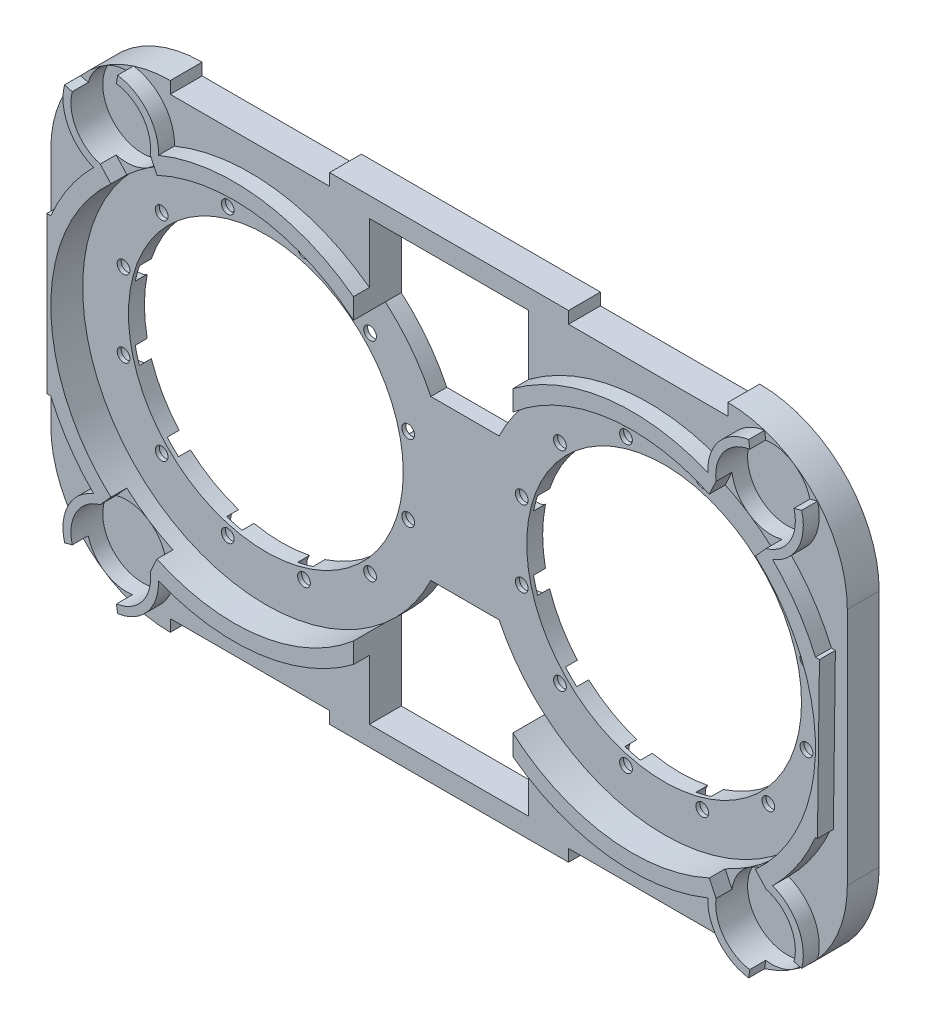
SolidWorks part; units mm, degrees
ref_plane "前视基准面" through (0, 0, 0) normal (0, 0, 1) x (1, 0, 0)
ref_plane "上视基准面" through (0, 0, 0) normal (0, 1, 0) x (1, 0, 0)
ref_plane "右视基准面" through (0, 0, 0) normal (1, 0, 0) x (0, 0, -1)
sketch "草图1" plane through (0, 0, 0) normal (0, 0, 1) x (1, 0, 0)
  line L0 (100, 30) -> (100, -30)
  line L1 (-20, -55) -> (20, -55)
  line L2 (-70, -60) -> (70, -60)
  line L3 (0, -20) -> (-8.5754, -20)
  line L4 (-100, 30) -> (-100, -30)
  line L10 (-70, 60) -> (70, 60)
  line L12 (8.5754, -20) -> (0, -20)
  line L13 (20, -55) -> (20, -34.8712)
  line L14 (-20, -55) -> (-20, -34.8712)
  line L16 (-20, 55) -> (20, 55)
  line L17 (-20, 55) -> (-20, 34.8712)
  line L18 (20, 55) -> (20, 34.8712)
  line L19 (8.5754, 20) -> (0, 20)
  line L20 (0, 20) -> (-8.5754, 20)
  circle A0 centre (-50, 0) radius 34.5
  circle A1 centre (50, 0) radius 34.5
  arc A2 (-100, 30) -> (-70, 60) centre (-70, 30) cw
  arc A3 (-100, -30) -> (-70, -60) centre (-70, -30) ccw
  arc A4 (100, -30) -> (70, -60) centre (70, -30) cw
  arc A5 (100, 30) -> (70, 60) centre (70, 30) ccw
  arc A8 (-8.5754, -20) -> (-20, -34.8712) centre (-50, 0) cw
  arc A9 (8.5754, -20) -> (20, -34.8712) centre (50, 0) ccw
  arc A10 (8.5754, 20) -> (20, 34.8712) centre (50, 0) cw
  arc A11 (-8.5754, 20) -> (-20, 34.8712) centre (-50, 0) ccw
  point P3 (0, -60)
  point P17 (-100, 0)
extrude "面板" add sketch "草图1" against normal blind 4 contours L0 A5 L10 A2 L4 A3 L2 A4 A1 A0 L12 A9 L13 L1 L14 A8 L3 L20 A11 L17 L16 L18 A10 L19 region at (0, 0, 0)
sketch "草图2" plane through (0, 0, 0) normal (0, 0, 1) x (1, 0, 0)
  line L0 (-100, 30) -> (-100, -30)
  line L3 (20, 55) -> (20, 34.8712)
  line L6 (-70, 60) -> (70, 60)
  line L7 (20, 55) -> (-20, 55)
  line L9 (-20, 55) -> (-20, 34.8712)
  line L12 (-70, -60) -> (70, -60)
  line L17 (100, 30) -> (100, -30)
  line L18 (8.5754, 20) -> (-8.5754, 20)
  line L25 (-20, -55) -> (-20, -34.8712)
  line L26 (8.5754, -20) -> (-8.5754, -20)
  line L27 (20, -55) -> (-20, -55)
  line L28 (20, -55) -> (20, -34.8712)
  arc A1 (-100, 30) -> (-70, 60) centre (-70, 30) cw
  arc A2 (-70, 60) -> (-100, 30) centre (-70, 30) ccw construction
  arc A4 (-100, -30) -> (-70, -60) centre (-70, -30) ccw
  arc A5 (100, -30) -> (70, -60) centre (70, -30) cw
  arc A7 (100, 30) -> (70, 60) centre (70, 30) ccw
  circle A20 centre (50, 0) radius 33
  circle A21 centre (-50, 0) radius 33
  arc A22 (8.5754, 20) -> (20, 34.8712) centre (50, 0) cw
  arc A23 (20, 34.8712) -> (8.5754, 20) centre (50, 0) ccw construction
  arc A24 (-8.5754, 20) -> (-20, 34.8712) centre (-50, 0) ccw
  arc A25 (-8.5754, 20) -> (-20, 34.8712) centre (-50, 0) ccw construction
  arc A26 (-8.5754, -20) -> (-20, -34.8712) centre (-50, 0) cw
  arc A27 (8.5754, -20) -> (20, -34.8712) centre (50, 0) ccw
  circle A28 centre (-50, 0) radius 46
  circle A29 centre (50, 0) radius 46
  circle A32 centre (80.95, 46.6721) radius 10
  circle A35 centre (-80.95, 46.6721) radius 10
  circle A36 centre (80.95, -46.6721) radius 10
  circle A37 centre (-80.95, -46.6721) radius 10
  point P7 (0, 0)
extrude "凸台-拉伸1" add sketch "草图2" along normal blind 4 contours L17 A7 L6 A1 L0 A4 L12 A5 A32 A29 A28 L18 A24 L9 L7 L3 A22 L26 A27 L28 L27 L25 A26 A36 A37 region at (-91.0483, 51.0483, 0)
sketch "草图3" plane through (0, 0, 0) normal (0, 0, 1) x (1, 0, 0)
  line L15 (-30, -57) -> (-70, -57)
  line L16 (70, 57) -> (70, 60.1247)
  line L17 (30, 60.1247) -> (30, 57)
  line L18 (70, 60.1247) -> (30, 60.1247)
  line L19 (30, 57) -> (70, 57)
  line L20 (-30, 57) -> (-30, 60)
  line L21 (-70, 60) -> (-30, 60)
  line L22 (-70, 57) -> (-70, 60)
  line L23 (-30, 57) -> (-70, 57)
  line L24 (-70, -57) -> (-70, -60)
  line L25 (-70, -60) -> (-30, -60)
  line L26 (-30, -57) -> (-30, -60)
  line L27 (30, -57) -> (70, -57)
  line L28 (70, -60.1247) -> (30, -60.1247)
  line L29 (30, -60.1247) -> (30, -57)
  line L30 (70, -57) -> (70, -60.1247)
extrude "切除-拉伸1" cut sketch "草图3" against normal blind 4 and the other way blind 4
hole_wizard "M3 六角凹头盖的柱孔2" positions "3D草图3" profile "草图6" counterbore size "M3" standard "BSI" end condition through all
sketch3d "3D草图3"
  point P34 (76.163, 26.163, -4)
  point P36 (59.5763, 35.7393, -4)
  point P38 (59.5763, 35.7393, -4)
  point P40 (40.4237, 35.7393, -4)
  point P42 (23.837, 26.163, -4)
  point P44 (14.2607, 9.5763, -4)
  point P46 (14.2607, -9.5763, -4)
  point P48 (23.837, -26.163, -4)
  point P50 (40.4237, -35.7393, -4)
  point P52 (59.5763, 35.7393, -4)
  point P54 (85.7393, -9.6269, -4)
  point P56 (85.7393, 9.5763, -4)
  point P94 (59.5763, -35.7393, -4)
  point P96 (59.5763, 35.7393, -4)
  point P98 (76.163, -26.163, -4)
  point P157 (-40.4237, 35.7393, -4)
  point P159 (-59.5763, 35.7393, -4)
  point P161 (-76.163, 26.163, -4)
  point P163 (-85.7393, 9.5763, -4)
  point P165 (-85.7393, -9.5763, -4)
  point P167 (-76.163, -26.163, -4)
  point P169 (-59.5763, -35.7393, -4)
  point P171 (-40.4237, -35.7393, -4)
  point P173 (-23.837, -26.163, -4)
  point P175 (-14.2607, -9.5763, -4)
  point P177 (-14.2607, 9.5763, -4)
  point P179 (-23.837, 26.163, -4)
sketch "草图6" plane through (76.163, 26.163, -4) normal (1, 0, 0) x (0, 1, 0)
  line L0 (0, 0) -> (0, 8)
  line L1 (0, 8) -> (1.6, 8)
  line L3 (1.6, 8) -> (1.6, 3)
  line L4 (1.6, 3) -> (3.25, 3)
  line L5 (3.25, 3) -> (3.25, 0)
  line L7 (3.25, 0) -> (0, 0)
  line L11 (0, -6.35) -> (0, 107.95) construction
  dimension "通孔孔直径" = 3.2
  dimension "通孔孔深度" = 8
  dimension "柱形沉头孔直径" = 6.5
  dimension "柱形沉头孔深度" = 3
ref_plane "基准面1" through (0, 0, 4) normal (0, 0, 1) x (1, 0, 0)
sketch "草图7" plane through (0, 0, 4) normal (0, 0, 1) x (1, 0, 0)
  line L8 (-79.2227, -58.5472) -> (-79.5106, -56.568)
  line L9 (-92.5339, 49.8046) -> (-90.6033, 49.2825)
  line L10 (-20, 34.8712) -> (-20, 40)
  line L11 (79.2227, 58.5472) -> (79.5106, 56.568)
  line L13 (-83.5982, 37.0292) -> (-80.9104, 34.0668)
  line L14 (71.0365, 45.3593) -> (69.3536, 41.7305)
  line L15 (-71.0365, 45.3593) -> (-69.3536, 41.7305)
  line L16 (83.5982, 37.0292) -> (80.9104, 34.0668)
  line L18 (20, 34.8712) -> (20, 40)
  line L19 (92.5339, 49.8046) -> (90.6033, 49.2825)
  line L20 (-79.2227, 58.5472) -> (-79.5106, 56.568)
  line L21 (92.5339, -49.8046) -> (90.6033, -49.2825)
  line L22 (20, -34.8712) -> (20, -40)
  line L23 (83.5982, -37.0292) -> (80.9104, -34.0668)
  line L24 (-71.0365, -45.3593) -> (-69.3536, -41.7305)
  line L25 (71.0365, -45.3593) -> (69.3536, -41.7305)
  line L26 (-83.5982, -37.0292) -> (-80.9104, -34.0668)
  line L27 (79.2227, -58.5472) -> (79.5106, -56.568)
  line L28 (-20, -34.8712) -> (-20, -40)
  line L29 (-92.5339, -49.8046) -> (-90.6033, -49.2825)
  line L30 (96, 19.5959) -> (97, 19.5959)
  line L31 (97, 19.5959) -> (96.5, -19.5959)
  line L32 (96.5, -19.5959) -> (96, -19.5959)
  line L33 (-96, 19.5959) -> (-97, 19.5959)
  line L34 (-97, 19.5959) -> (-97, -19.5959)
  line L35 (-97, -19.5959) -> (-96, -19.5959)
  arc A17 (79.5106, 56.568) -> (71.0365, 45.3593) centre (80.95, 46.6721) ccw
  arc A19 (20, 34.8712) -> (69.3536, 41.7305) centre (50, 0) cw
  arc A20 (20, 40) -> (68.9568, 46.267) centre (50, 0) cw
  arc A21 (96, 19.5959) -> (85.2437, 35.4666) centre (50, 0) ccw
  arc A22 (-80.9104, 34.0668) -> (-80.9104, -34.0668) centre (-50, 0) ccw
  arc A24 (90.6033, 49.2825) -> (83.5982, 37.0292) centre (80.95, 46.6721) cw
  arc A25 (79.2227, 58.5472) -> (68.9568, 46.267) centre (80.95, 46.6721) ccw
  arc A26 (100, 30) -> (70, 60) centre (70, 30) ccw construction
  arc A27 (92.5339, 49.8046) -> (85.2437, 35.4666) centre (80.95, 46.6721) cw
  arc A28 (80.9104, 34.0668) -> (80.9104, -34.0668) centre (50, 0) cw
  arc A29 (-92.5339, 49.8046) -> (-85.2437, 35.4666) centre (-80.95, 46.6721) ccw
  arc A30 (-79.2227, 58.5472) -> (-68.9568, 46.267) centre (-80.95, 46.6721) cw
  arc A31 (-90.6033, 49.2825) -> (-83.5982, 37.0292) centre (-80.95, 46.6721) ccw
  arc A32 (-96, 19.5959) -> (-85.2437, 35.4666) centre (-50, 0) cw
  arc A33 (-20, 40) -> (-68.9568, 46.267) centre (-50, 0) ccw
  arc A34 (-20, 34.8712) -> (-69.3536, 41.7305) centre (-50, 0) ccw
  arc A35 (-79.5106, 56.568) -> (-71.0365, 45.3593) centre (-80.95, 46.6721) cw
  arc A36 (-79.5106, -56.568) -> (-71.0365, -45.3593) centre (-80.95, -46.6721) ccw
  arc A37 (-20, -34.8712) -> (-69.3536, -41.7305) centre (-50, 0) cw
  arc A38 (-20, -40) -> (-68.9568, -46.267) centre (-50, 0) cw
  arc A39 (-96, -19.5959) -> (-85.2437, -35.4666) centre (-50, 0) ccw
  arc A40 (-90.6033, -49.2825) -> (-83.5982, -37.0292) centre (-80.95, -46.6721) cw
  arc A41 (-79.2227, -58.5472) -> (-68.9568, -46.267) centre (-80.95, -46.6721) ccw
  arc A42 (-92.5339, -49.8046) -> (-85.2437, -35.4666) centre (-80.95, -46.6721) cw
  arc A43 (92.5339, -49.8046) -> (85.2437, -35.4666) centre (80.95, -46.6721) ccw
  arc A44 (79.2227, -58.5472) -> (68.9568, -46.267) centre (80.95, -46.6721) cw
  arc A45 (90.6033, -49.2825) -> (83.5982, -37.0292) centre (80.95, -46.6721) ccw
  arc A46 (96, -19.5959) -> (85.2437, -35.4666) centre (50, 0) cw
  arc A47 (20, -40) -> (68.9568, -46.267) centre (50, 0) ccw
  arc A48 (20, -34.8712) -> (69.3536, -41.7305) centre (50, 0) ccw
  arc A49 (79.5106, -56.568) -> (71.0365, -45.3593) centre (80.95, -46.6721) cw
  point P7 (96, 0)
  point P70 (-96, 0)
extrude "凸台-拉伸9" add sketch "草图7" along normal blind 4
